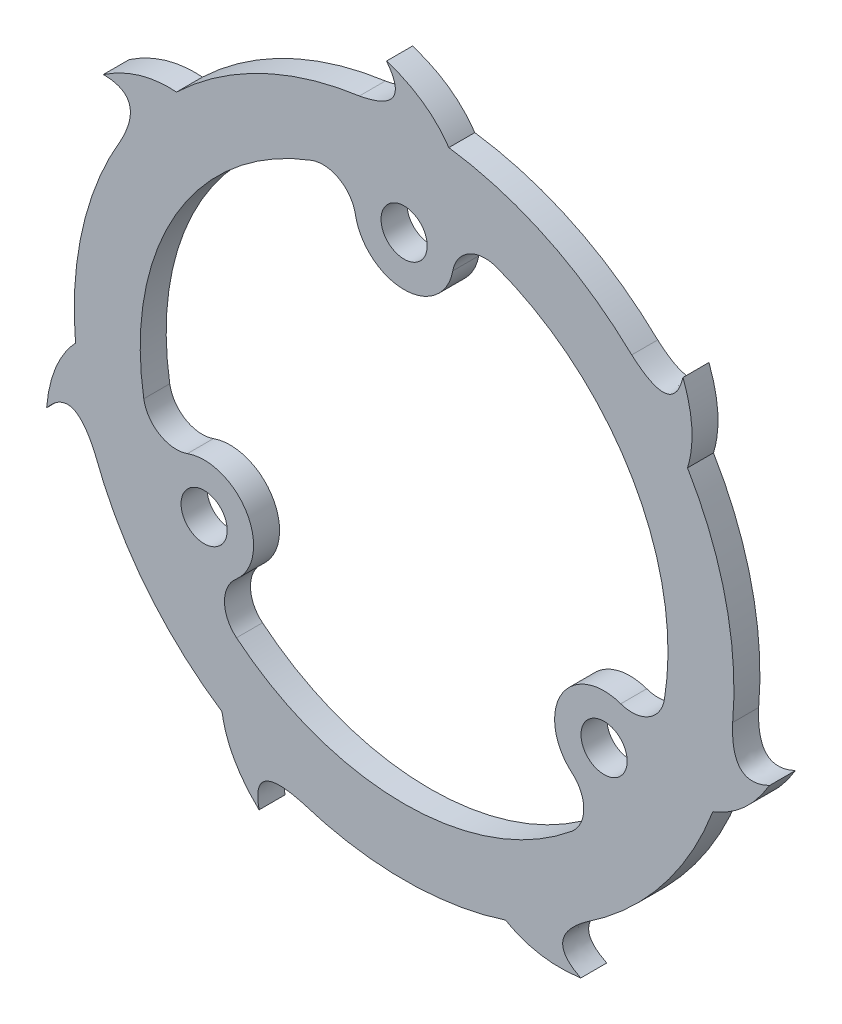
SolidWorks part; units mm, degrees
ref_plane "Front Plane" through (0, 0, 0) normal (0, 0, 1) x (1, 0, 0)
ref_plane "Top Plane" through (0, 0, 0) normal (0, 1, 0) x (1, 0, 0)
ref_plane "Right Plane" through (0, 0, 0) normal (1, 0, 0) x (0, 0, -1)
sketch "Sketch1" plane through (0, 0, 0) normal (0, 0, 1) x (1, 0, 0)
  line L0 (0, 0) -> (0, 17.78) construction
  line L1 (0, 17.78) -> (0, 20.32) construction
  line L2 (-3.81, 17.78) -> (-3.81, 19.9596)
  line L3 (3.81, 17.78) -> (3.81, 19.9596)
  line L8 (13.4929, -12.1896) -> (15.3805, -13.2794)
  line L9 (17.3029, -5.5904) -> (19.1905, -6.6803)
  line L12 (-17.3029, -5.5904) -> (-19.1905, -6.6803)
  line L13 (-13.4929, -12.1896) -> (-15.3805, -13.2794)
  circle A0 centre (0, 17.78) radius 1.778
  arc A1 (21.997, 12.7) -> (-21.997, 12.7) centre (0, 0) ccw
  arc A2 (-3.81, 19.9596) -> (-17.5976, 10.16) centre (0, 0) ccw
  arc A3 (-3.81, 17.78) -> (3.81, 17.78) centre (0, 17.78) ccw
  arc A5 (17.5976, 10.16) -> (3.81, 19.9596) centre (0, 0) ccw
  arc A6 (0, -25.4) -> (21.997, 12.7) centre (0, 0) ccw
  arc A7 (0, -20.32) -> (15.3805, -13.2794) centre (0, 0) ccw
  arc A8 (17.3029, -5.5904) -> (13.4929, -12.1896) centre (15.3979, -8.89) ccw
  arc A9 (19.1905, -6.6803) -> (17.5976, 10.16) centre (0, 0) ccw
  circle A10 centre (15.3979, -8.89) radius 1.778
  arc A11 (-21.997, 12.7) -> (0, -25.4) centre (0, 0) ccw
  arc A12 (-17.5976, 10.16) -> (-19.1905, -6.6803) centre (0, 0) ccw
  arc A13 (-13.4929, -12.1896) -> (-17.3029, -5.5904) centre (-15.3979, -8.89) ccw
  arc A14 (-15.3805, -13.2794) -> (0, -20.32) centre (0, 0) ccw
  circle A15 centre (-15.3979, -8.89) radius 1.778
  point P6 (0, 19.05)
  point P37 (0, 0)
  dimension "D1" = 17.78
  dimension "D2" = 3.556
  dimension "D3" = 50.8
  dimension "D4" = 40.64
  dimension "D7" = 3
extrude "Boss-Extrude1" add sketch "Sketch1" along normal blind 2
sketch "Sketch2" plane through (0, 0, 2) normal (0, 0, 1) x (1, 0, 0)
  line L0 (0, 25.4) -> (-1.3515, 28.543) construction
  line L1 (-1.3515, 28.543) -> (3.4442, 25.1654) construction
  line L2 (-3.4442, 25.1654) -> (4.3882, 23.3294)
  line L3 (17.5277, 18.3831) -> (20.9756, 11.1147)
  line L4 (19.8585, 15.8366) -> (21.4732, 18.8529) construction
  line L5 (21.4732, 18.8529) -> (21.8225, 12.9976) construction
  line L6 (25.3009, -2.242) -> (21.768, -9.4695)
  line L7 (24.7632, -5.652) -> (28.1281, -5.0338) construction
  line L8 (28.1281, -5.0338) -> (23.7681, -8.9577) construction
  line L9 (14.022, -21.1789) -> (6.1686, -22.923)
  line L10 (11.0206, -22.8846) -> (13.602, -25.13) construction
  line L11 (13.602, -25.13) -> (7.8158, -24.1676) construction
  line L12 (-7.8158, -24.1676) -> (-14.0759, -19.115)
  line L13 (-11.0206, -22.8846) -> (-11.1667, -26.3028) construction
  line L14 (-11.1667, -26.3028) -> (-14.022, -21.1789) construction
  line L15 (-23.7681, -8.9577) -> (-23.7209, -0.913)
  line L16 (-24.7632, -5.652) -> (-27.5267, -7.669) construction
  line L17 (-27.5267, -7.669) -> (-25.3009, -2.242) construction
  line L18 (-21.8225, 12.9976) -> (-15.5036, 17.9765)
  line L19 (-19.8585, 15.8366) -> (-23.1585, 16.7397) construction
  line L20 (-23.1585, 16.7397) -> (-17.5277, 18.3831) construction
  circle A0 centre (0, 0) radius 28.575 construction
  circle A1 centre (0, 0) radius 25.4 construction
  circle A2 centre (0, 0) radius 25.4
  spline S0 degree 1 poles (-0.6757, 26.9715) (0, 25.4) knots 0 0 1 1
  spline S1 degree 2 poles (-1.3515, 28.543) (0.6935, 25.9205) (-3.4442, 25.1654) knots 0 0 0 1 1 1
  spline S2 degree 2 poles (-1.3515, 28.543) (2.947, 27.1793) (4.3882, 23.3294) knots 0 0 0 1 1 1
  spline S3 degree 1 poles (20.6659, 17.3448) (19.8585, 15.8366) knots 0 0 1 1
  spline S4 degree 2 poles (21.4732, 18.8529) (20.6979, 15.619) (17.5277, 18.3831) knots 0 0 0 1 1 1
  spline S5 degree 2 poles (21.4732, 18.8529) (23.087, 14.6419) (20.9756, 11.1147) knots 0 0 0 1 1 1
  spline S6 degree 1 poles (26.4456, -5.3429) (24.7632, -5.652) knots 0 0 1 1
  spline S7 degree 2 poles (28.1281, -5.0338) (25.1163, -6.444) (25.3009, -2.242) knots 0 0 0 1 1 1
  spline S8 degree 2 poles (28.1281, -5.0338) (25.842, -8.9211) (21.768, -9.4695) knots 0 0 0 1 1 1
  spline S9 degree 1 poles (12.3113, -24.0073) (11.0206, -22.8846) knots 0 0 1 1
  spline S10 degree 2 poles (13.602, -25.13) (10.6217, -23.6545) (14.022, -21.1789) knots 0 0 0 1 1 1
  spline S11 degree 2 poles (13.602, -25.13) (9.1375, -25.7663) (6.1686, -22.923) knots 0 0 0 1 1 1
  spline S12 degree 1 poles (-11.0937, -24.5937) (-11.0206, -22.8846) knots 0 0 1 1
  spline S13 degree 2 poles (-11.1667, -26.3028) (-11.8713, -23.0527) (-7.8158, -24.1676) knots 0 0 0 1 1 1
  spline S14 degree 2 poles (-11.1667, -26.3028) (-14.4478, -23.209) (-14.0759, -19.115) knots 0 0 0 1 1 1
  spline S15 degree 1 poles (-26.1449, -6.6605) (-24.7632, -5.652) knots 0 0 1 1
  spline S16 degree 2 poles (-27.5267, -7.669) (-25.425, -5.0918) (-23.7681, -8.9577) knots 0 0 0 1 1 1
  spline S17 degree 2 poles (-27.5267, -7.669) (-27.1536, -3.1748) (-23.7209, -0.913) knots 0 0 0 1 1 1
  spline S18 degree 1 poles (-21.5085, 16.2882) (-19.8585, 15.8366) knots 0 0 1 1
  spline S19 degree 2 poles (-23.1585, 16.7397) (-19.8331, 16.7034) (-21.8225, 12.9976) knots 0 0 0 1 1 1
  spline S20 degree 2 poles (-23.1585, 16.7397) (-19.4122, 19.2501) (-15.5036, 17.9765) knots 0 0 0 1 1 1
  point P64 (0, 0)
  dimension "D1" = 57.15
  dimension "D2" = 7
extrude "Boss-Extrude2" add sketch "Sketch2" against normal up to surface (2 mm away) contours S2 L2 S1 | S5 L3 S4 | S8 L6 S7 | S11 L9 S10 | S14 L12 S13 | S17 L15 S16 | S20 L18 S19 up to face at (1.778, 17.78, 0)
fillet "Fillet1" radius 2.54 6 edges at (19.1905, -6.6803, 1) (15.3805, -13.2794, 1) (-15.3805, -13.2794, 1) (-19.1905, -6.6803, 1) (-3.81, 19.9596, 1) (3.81, 19.9596, 1)
